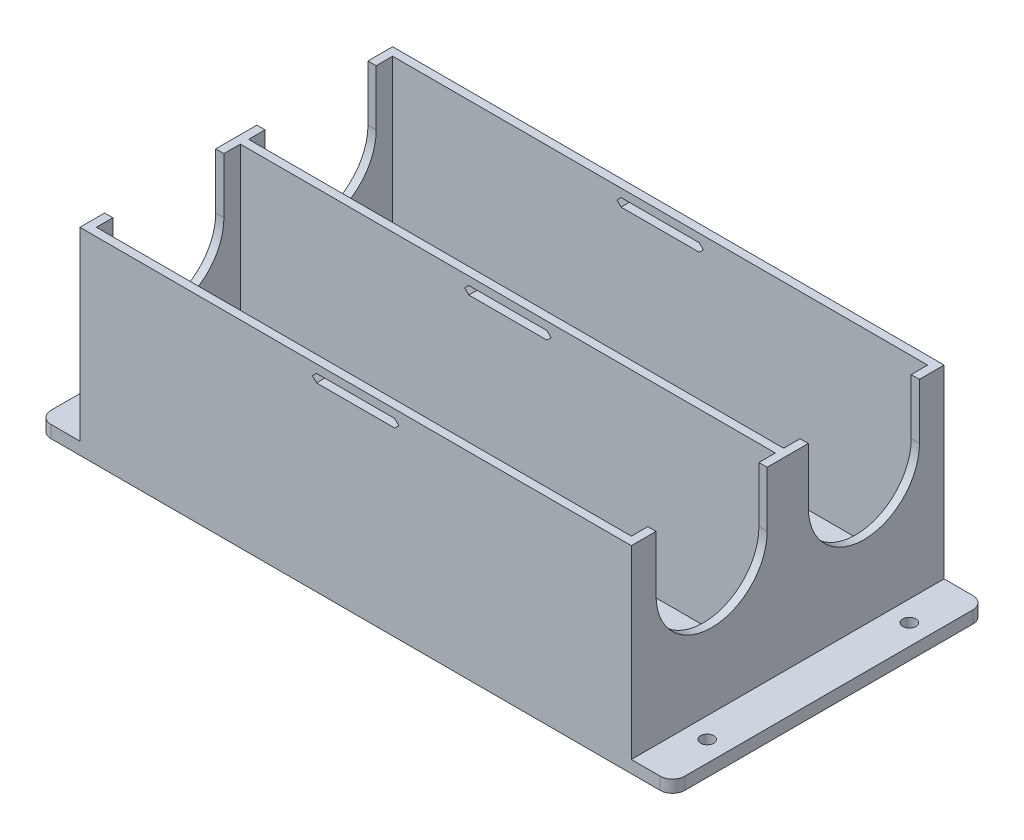
SolidWorks part; units mm, degrees
ref_plane "Front Plane" through (0, 0, 0) normal (0, 0, 1) x (1, 0, 0)
ref_plane "Top Plane" through (0, 0, 0) normal (0, 1, 0) x (1, 0, 0)
ref_plane "Right Plane" through (0, 0, 0) normal (1, 0, 0) x (0, 0, -1)
sketch "Szkic1" plane through (0, 0, 0) normal (0, 1, 0) x (1, 0, 0)
  line L0 (-65, -36) -> (65, 36) construction
  line L1 (-65, 36) -> (65, 36)
  line L2 (-65, 36) -> (-65, -36)
  line L3 (-65, -36) -> (65, -36)
  line L4 (65, 36) -> (65, -36)
  line L5 (-67, 38) -> (67, 38)
  line L6 (67, 38) -> (67, -38)
  line L7 (-67, -38) -> (67, -38)
  line L8 (-67, 38) -> (-67, -38)
  line L10 (-65, 1) -> (65, 1)
  line L11 (-65, 1) -> (-65, -1)
  line L12 (-65, -1) -> (65, -1)
  line L13 (65, 1) -> (65, -1)
  line L14 (65, 33.5) -> (-65, 33.5) construction
  line L16 (0, -55) -> (0, 55) construction
  line L17 (-67, 38) -> (-77, 38)
  line L18 (-67, 38) -> (-67, -38)
  line L19 (-67, -38) -> (-77, -38)
  line L20 (-77, 38) -> (-77, -38)
  line L21 (67, -38) -> (77, -38)
  line L22 (77, 38) -> (77, -38)
  line L23 (67, 38) -> (77, 38)
  line L24 (67, 38) -> (67, -38)
  point P13 (-65, 0)
  dimension "D2" = 2
  dimension "D3" = 35
  dimension "D4" = 10
  dimension "D1" = 2
extrude "Dodanie-wyciągnięcie1" add sketch "Szkic1" along normal blind 3 contours L17 L20 L19 L8 | L23 L6 L21 L22 | L8 L7 L6 L5 region at (-72, 0, 0) region at (72, 0, 0)
extrude "Dodanie-wyciągnięcie2" add sketch "Szkic1<3>" along normal offset from surface (48 mm away) 3 contours L5 L8 L7 L6 L1 L4 L3 L2 | L12 L13 L10 L11 region at (0, 0, -36.4595) offset beyond the face yes
sketch "Szkic1<3>" plane through (0, 0, 0) normal (0, 1, 0) x (1, 0, 0) same geometry as "Szkic1"
sketch "Szkic2" plane through (-67, 0, 0) normal (-1, 0, 0) x (0, 0, 1)
  line L0 (-38, 48) -> (38, 48) construction
  line L1 (-32, 48) -> (-5, 48)
  line L2 (-32, 48) -> (-32, 34.5)
  line L3 (-32, 34.5) -> (-5, 34.5)
  line L4 (-5, 48) -> (-5, 34.5)
  line L5 (-36, 48) -> (-36, 3) construction
  line L10 (-1, 3) -> (-1, 48) construction
  line L11 (0, -18.1629) -> (0, 18.1629) construction
  line L12 (32, 34.5) -> (5, 34.5)
  line L13 (5, 48) -> (5, 34.5)
  line L14 (32, 48) -> (5, 48)
  line L15 (32, 48) -> (32, 34.5)
  circle A0 centre (-18.5, 34.5) radius 13.5
  circle A2 centre (18.5, 34.5) radius 13.5
  line M8 (38, 48) -> (-38, 48)
  dimension "D1" = 4
  dimension "D2" = 4
extrude "Wytnij-wyciągnięcie1" cut sketch "Szkic2" against normal through all contours L3 A0 | L3 A0 | A0 L1 L2 | A0 L4 M8 | A2 L12 | A2 L12 | L13 A2 L14 | A2 L15 M8 region at (-67, 44.9845, 8.0155) region at (-67, 44.9845, -28.9845) region at (-67, 44.9845, -8.0155) region at (-67, 40.2296, -18.5) region at (-67, 28.7704, -18.5) region at (-67, 40.2296, 18.5) region at (-67, 28.7704, 18.5) region at (-67, 44.9845, 28.9845)
hole_wizard "M3 Clearance Hole1" positions "Szkic3" profile "Szkic4" hole size "M3" standard "DIN"
sketch "Szkic3" plane through (0, 3, 0) normal (0, 1, 0) x (1, 0, 0)
  line L0 (-72, 24.5653) -> (-72, 38) construction
  line L1 (-67, 38) -> (-77, 38) construction
  line L3 (-72, -24.5653) -> (-72, -38) construction
  line L4 (-67, -38) -> (-77, -38) construction
  line L6 (77, -38) -> (67, -38) construction
  line L7 (72, -38) -> (72, -24.5653) construction
  point P0 (-72, 24.5653)
  point P2 (-72, -24.5653)
  point P4 (72, -24.5653)
  point P6 (72, 24.5653)
  point P30 (0, 0)
sketch "Szkic4" plane through (-72, 3, -24.5653) normal (1, 0, 0) x (0, 0, 1)
  line L0 (0, 0) -> (0, 8.6614)
  line L1 (0, 8.6614) -> (1.6, 7.7)
  line L2 (1.6, 7.7) -> (1.6, 0)
  line L5 (1.6, 0) -> (0, 0)
  line L10 (0, 8.6614) -> (-1.6, 7.7) construction
  line L11 (0, -6.35) -> (0, 107.95) construction
  dimension "Hole Dia." = 3.2
  dimension "Hole Depth" = 7.7
  dimension "Drill Angle" = 118
fillet "Zaokrąglenie1" radius 3 4 edges at (77, 1.5, -38) (77, 1.5, 38) (-77, 1.5, -38) (-77, 1.5, 38)
sketch "Szkic6" plane through (0, 0, 38) normal (0, 0, 1) x (1, 0, 0)
  line L0 (-67, 48) -> (67, 48) construction
  line L1 (-10.5, 46) -> (10.5, 46)
  line L2 (-10.5, 46) -> (-10.5, 44)
  line L3 (-10.5, 44) -> (10.5, 44)
  line L4 (10.5, 46) -> (10.5, 44)
  line L5 (0, -26.4) -> (0, 26.4) construction
  point P8 (0, 46)
  dimension "D1" = 2
  dimension "D2" = 2
  dimension "D3" = 21
extrude "Wytnij-wyciągnięcie2" cut sketch "Szkic6" against normal through all
chamfer "Sfazowanie1" distance 1 angle 45 12 edges at (10.5, 44, 37) (10.5, 46, 37) (-10.5, 46, 37) (-10.5, 44, 37) (10.5, 46, -37) (10.5, 44, -37) (-10.5, 46, -37) (-10.5, 44, -37) (-10.5, 46, 0) (-10.5, 44, 0) (10.5, 46, 0) (10.5, 44, 0)
